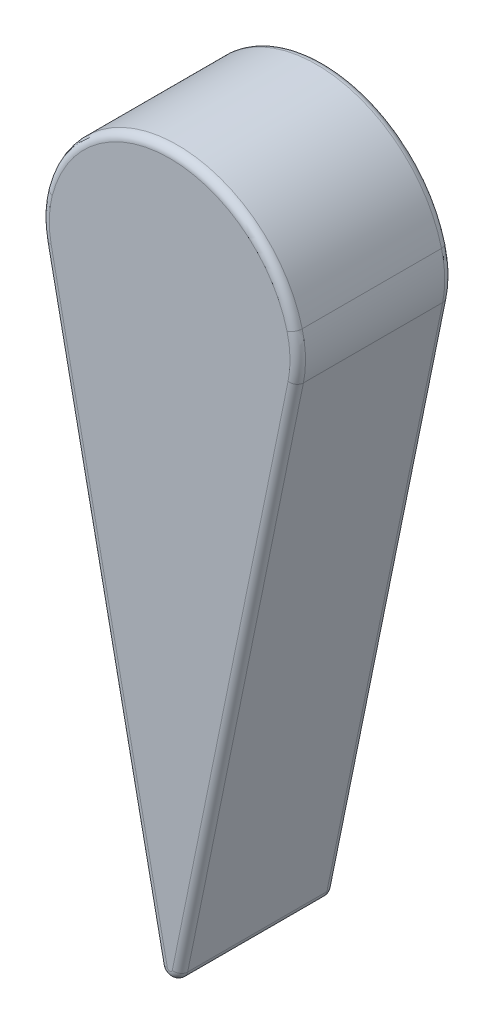
SolidWorks part; units mm, degrees
ref_plane "Front" through (0, 0, 0) normal (0, 0, 1) x (1, 0, 0)
ref_plane "Top" through (0, 0, 0) normal (0, 1, 0) x (1, 0, 0)
ref_plane "Right" through (0, 0, 0) normal (1, 0, 0) x (0, 0, -1)
sketch "Sketch1" plane through (0, 0, 0) normal (0, 0, 1) x (1, 0, 0)
  line L0 (-0.5, 0) -> (0.0007, -2.4496)
  line L1 (0.0007, -2.4496) -> (0.5, 0)
  circle A0 centre (0, 0) radius 0.5
extrude "Boss-Extrude1" add sketch "Sketch1" along normal blind 0.6 contours L1 A0 L0 | A0 L0 L1 region at (0, 0.0003, 0) region at (0.0003, -1.0985, 0)
fillet "Fillet1" radius 0.04 1 edges at (0.0007, -2.4496, 0.3)
fillet "Fillet2" radius 0.4 2 edges at (0.5, 0, 0.3) (-0.5, 0, 0.3)
fillet "Fillet3" radius 0.03 12 edges at (-0.4967, 0.0351, 0) (-0.2637, -1.1564, 0) (0.0006, -2.2896, 0) (0.2643, -1.1563, 0) (0.4967, 0.035, 0) (0.0002, 0.5, 0) (0.0006, -2.2896, 0.6) (-0.2637, -1.1564, 0.6) (-0.4967, 0.0351, 0.6) (0.0002, 0.5, 0.6) (0.4967, 0.035, 0.6) (0.2643, -1.1563, 0.6)
